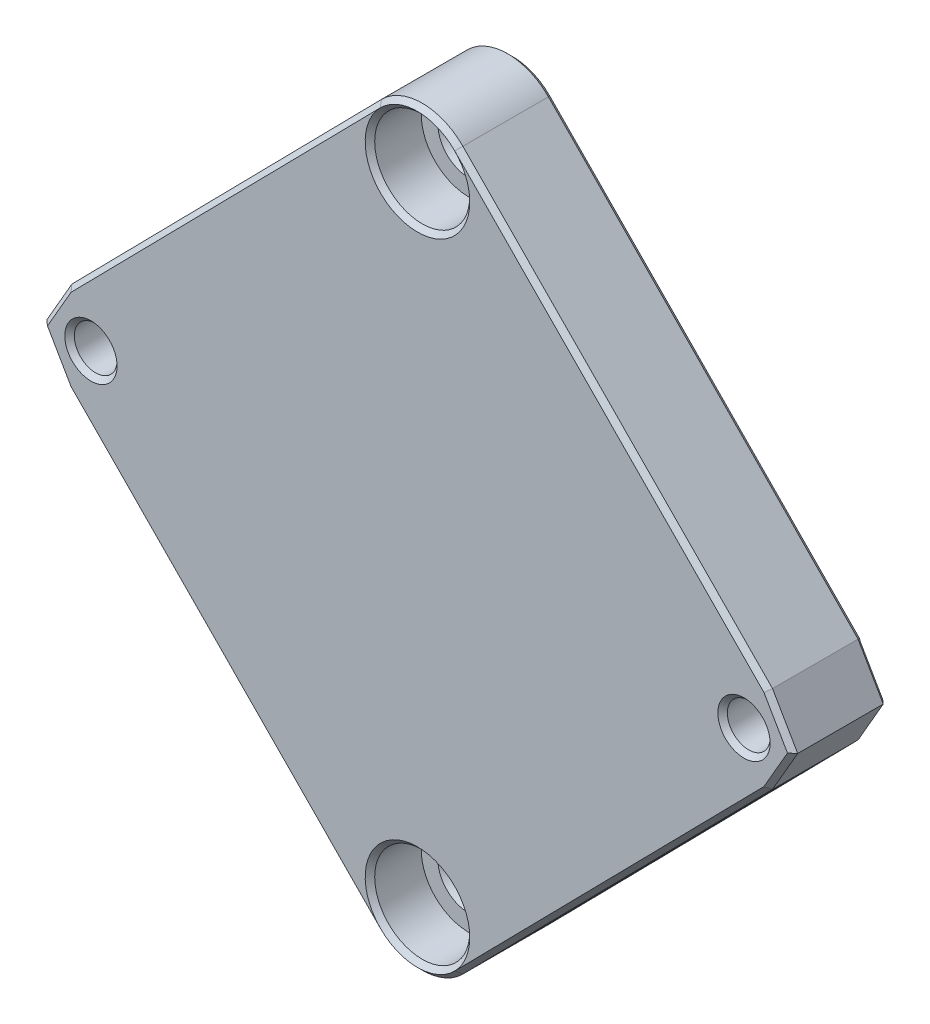
SolidWorks part; units mm, degrees
ref_plane "Top" through (0, 0, 0) normal (0, 0, 1) x (1, 0, 0)
ref_plane "Front" through (0, 0, 0) normal (0, 1, 0) x (1, 0, 0)
ref_plane "Right" through (0, 0, 0) normal (1, 0, 0) x (0, 0, -1)
sketch "Sketch1" plane through (0, 0, 0) normal (0, 0, 1) x (1, 0, 0)
  line L1 (0, 0) -> (79, 0)
  line L2 (0, 0) -> (0, 87)
  line L3 (0, 87) -> (79, 87)
  line L4 (79, 0) -> (79, 87)
  dimension "D1" = 79
  dimension "D2" = 87
extrude "Boss-Extrude1" add sketch "Sketch1" along normal blind 10
sketch "Sketch4" plane through (0, 0, 10) normal (0, 0, 1) x (1, 0, 0)
  line L0 (5.15, 43.5) -> (73.85, 43.5)
  line L2 (79, 0) -> (79, 87) construction
  line L5 (79, 87) -> (0, 87) construction
  point P2 (39.5, 43.5)
  dimension "D1" = 68.7
  dimension "D2" = 39.5
  dimension "D3" = 43.5
hole_wizard "M4 Clearance Hole1" positions "Sketch5" profile "Sketch6" hole size "M4" standard "DIN" end condition through all
sketch "Sketch5" plane through (0, 0, 10) normal (0, 0, 1) x (1, 0, 0)
  point P0 (5.15, 43.5)
  point P3 (73.85, 43.5)
sketch "Sketch6" plane through (5.15, 43.5, 10) normal (1, 0, 0) x (0, -1, 0)
  line L0 (0, 0) -> (0, 10)
  line L1 (0, 10) -> (2.25, 10)
  line L2 (2.25, 10) -> (2.25, 0)
  line L5 (2.25, 0) -> (0, 0)
  line L11 (0, -6.35) -> (0, 107.95) construction
  dimension "Thru Hole Dia." = 4.5
  dimension "Thru Hole Depth" = 10
sketch "Sketch11" plane through (0, 0, 0) normal (0, 0, -1) x (-1, 0, 0)
  line L0 (-79, 87) -> (0, 87) construction
  line L1 (-69.6353, 43.5) -> (-71.7427, 47.15)
  line L2 (-71.7427, 47.15) -> (-75.9573, 47.15)
  line L3 (-75.9573, 47.15) -> (-78.0647, 43.5)
  line L4 (-78.0647, 43.5) -> (-75.9573, 39.85)
  line L5 (-75.9573, 39.85) -> (-71.7427, 39.85)
  line L6 (-71.7427, 39.85) -> (-69.6353, 43.5)
  line L7 (-9.3647, 43.5) -> (-7.2573, 39.85)
  line L8 (-7.2573, 39.85) -> (-3.0427, 39.85)
  line L9 (-3.0427, 39.85) -> (-0.9353, 43.5)
  line L10 (-0.9353, 43.5) -> (-3.0427, 47.15)
  line L11 (-3.0427, 47.15) -> (-7.2573, 47.15)
  line L12 (-7.2573, 47.15) -> (-9.3647, 43.5)
  circle A0 centre (-73.85, 43.5) radius 3.65 construction
  circle A1 centre (-5.15, 43.5) radius 3.65 construction
  dimension "D1" = 7.3
  dimension "D2" = 7.3
extrude "Cut-Extrude3" cut sketch "Sketch11" against normal blind 3.5
sketch "Sketch12" plane through (0, 0, 10) normal (0, 0, -1) x (-1, 0, 0)
  line L0 (-39.5, 77) -> (-39.5, 10)
  line L1 (-79, 0) -> (-79, 87) construction
  line L3 (-79, 87) -> (0, 87) construction
  dimension "D1" = 39.5
  dimension "D2" = 67
  dimension "D3" = 10
hole_wizard "CBORE for M5 Socket Head Cap Screw1" positions "Sketch15" profile "Sketch16" counterbore size "M5" standard "DIN" end condition through all
sketch "Sketch15" plane through (0, 0, 10) normal (0, 0, 1) x (1, 0, 0)
  point P0 (39.5, 77)
  point P3 (39.5, 10)
sketch "Sketch16" plane through (39.5, 77, 10) normal (1, 0, 0) x (0, -1, 0)
  line L0 (0, 0) -> (0, 10)
  line L1 (0, 10) -> (2.75, 10)
  line L3 (2.75, 10) -> (2.75, 5.4)
  line L4 (2.75, 5.4) -> (5, 5.4)
  line L5 (5, 5.4) -> (5, 0)
  line L7 (5, 0) -> (0, 0)
  line L11 (0, -6.35) -> (0, 107.95) construction
  dimension "Thru Hole Dia." = 5.5
  dimension "Thru Hole Depth" = 10
  dimension "C'Bore Dia." = 10
  dimension "C'Bore Depth" = 5.4
sketch "Sketch17" plane through (0, 0, 0) normal (0, 0, -1) x (-1, 0, 0)
  line L0 (-76.3481, 48.0932) -> (-43.7776, 81.2074)
  line L2 (-35.2224, 81.2074) -> (-2.6519, 48.0932)
  line L4 (-76.3481, 38.9068) -> (-43.7776, 5.7926)
  line L5 (-35.2224, 5.7926) -> (-2.6519, 38.9068)
  line L14 (-2.6519, 38.9068) -> (0, 43.5)
  line L15 (0, 87) -> (0, 0) construction
  line L16 (0, 43.5) -> (-2.6519, 48.0932)
  line L17 (-0.9353, 43.5) -> (-3.0427, 47.15) construction
  line L18 (-3.0427, 39.85) -> (-0.9353, 43.5) construction
  line L20 (-76.3481, 48.0932) -> (-79, 43.5)
  line L21 (-79, 0) -> (-79, 87) construction
  line L22 (-79, 43.5) -> (-76.3481, 38.9068)
  line L23 (-78.0647, 43.5) -> (-75.9573, 39.85) construction
  line L24 (-75.9573, 47.15) -> (-78.0647, 43.5) construction
  line L25 (-125.188, 43.5) -> (-108.4403, 14.492)
  line L26 (-108.4403, 14.492) -> (-72.295, -22.2566)
  line L27 (-6.705, -22.2566) -> (29.4403, 14.492)
  line L28 (29.4403, 14.492) -> (46.188, 43.5)
  line L29 (46.188, 43.5) -> (29.4403, 72.508)
  line L30 (-6.705, 109.2566) -> (29.4403, 72.508)
  line L31 (-108.4403, 72.508) -> (-72.295, 109.2566)
  line L32 (-108.4403, 72.508) -> (-125.188, 43.5)
  arc A0 (-43.7776, 81.2074) -> (-35.2224, 81.2074) centre (-39.5, 77) cw
  arc A1 (-43.7776, 5.7926) -> (-35.2224, 5.7926) centre (-39.5, 10) ccw
  arc A4 (-72.295, -22.2566) -> (-6.705, -22.2566) centre (-39.5, 10) ccw
  arc A5 (-72.295, 109.2566) -> (-6.705, 109.2566) centre (-39.5, 77) cw
  dimension "D2" = 6
  dimension "D4" = 6
  dimension "D1" = 0.94
  dimension "D3" = 0.94
  dimension "D5" = 0.94
  dimension "D6" = 0.94
  dimension "D7" = 40
extrude "Cut-Extrude4" cut sketch "Sketch17" against normal blind 10
chamfer "Chamfer1" distance 0.5 angle 45 38 edges at (77.6741, 41.2034, 10) (60.0629, 22.3497, 10) (39.5, 4, 10) (18.9371, 22.3497, 10) (1.3259, 41.2034, 10) (1.3259, 45.7966, 10) (18.9371, 64.6503, 10) (39.5, 83, 10) (60.0629, 64.6503, 10) (77.6741, 45.7966, 10) (76.1, 43.5, 10) (7.4, 43.5, 10) (44.5, 10, 10) (44.5, 77, 10) (39.5, 83, 0) (18.9371, 64.6503, 0) (1.3259, 45.7966, 0) (1.3259, 41.2034, 0) (18.9371, 22.3497, 0) (39.5, 4, 0) (60.0629, 22.3497, 0) (77.6741, 41.2034, 0) (77.6741, 45.7966, 0) (60.0629, 64.6503, 0) (8.311, 41.675, 0) (5.15, 39.85, 0) (1.989, 41.675, 0) (1.989, 45.325, 0) (5.15, 47.15, 0) (8.311, 45.325, 0) (70.689, 45.325, 0) (73.85, 47.15, 0) (77.011, 45.325, 0) (77.011, 41.675, 0) (73.85, 39.85, 0) (70.689, 41.675, 0) (42.25, 10, 0) (42.25, 77, 0)
chamfer "Chamfer2" distance 0.5 angle 45 2 edges at (42.25, 10, 4.6) (42.25, 77, 4.6)
ref_plane "Plane1" through (0, 45.75, 0) normal (0, -1, 0) x (-1, 0, 0)
ref_axis "Axis1" through (39.5, 77, -10.3065) along (0, 0, 1)
ref_axis "Axis2" through (39.5, 10, 0.5) along (0, 0, 1)
ref_plane "Plane2" through (39.5, 0, 0) normal (-1, 0, 0) x (0, 0, 1)
